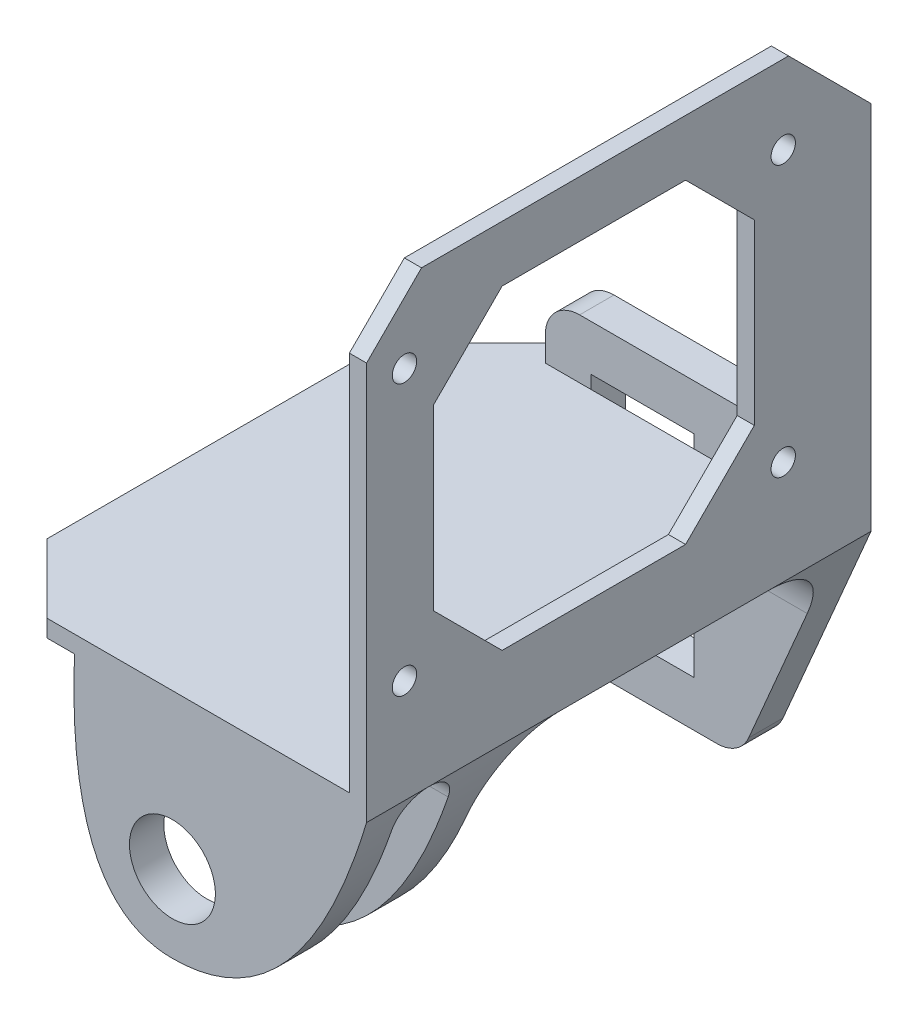
SolidWorks part; units mm, degrees
material "ABS PC"
ref_plane "Front Plane" through (0, 0, 0) normal (0, 0, 1) x (1, 0, 0)
ref_plane "Top Plane" through (0, 0, 0) normal (0, 1, 0) x (1, 0, 0)
ref_plane "Right Plane" through (0, 0, 0) normal (1, 0, 0) x (0, 0, -1)
sketch "Sketch1" plane through (0, 0, 0) normal (0, 1, 0) x (1, 0, 0)
  line L0 (0, 46.609) -> (71.755, 46.609) construction
  line L1 (0, 0) -> (71.755, 0)
  line L2 (0, 0) -> (0, 93.218)
  line L3 (0, 93.218) -> (71.755, 93.218)
  line L4 (71.755, 0) -> (71.755, 93.218)
  line L5 (35.8775, 93.218) -> (35.8775, 0) construction
  dimension "D1" = 71.755
  dimension "D2" = 93.218
extrude "Boss-Extrude1" add sketch "Sketch1" along normal blind 3.175
ref_plane "Plane2" through (0, 0, -46.609) normal (0, 0, -1) x (-1, 0, 0)
ref_plane "Plane1" through (35.8775, 0, 0) normal (1, 0, 0) x (0, 0, -1)
sketch "Sketch3" plane through (0, 3.175, 0) normal (0, 1, 0) x (1, 0, 0)
  line L0 (71.755, 0) -> (68.58, 0)
  line L1 (0, 0) -> (71.755, 0) construction
  line L2 (68.58, 0) -> (68.58, 93.218)
  line L3 (71.755, 93.218) -> (0, 93.218) construction
  line L4 (68.58, 93.218) -> (71.755, 93.218)
  line L5 (71.755, 93.218) -> (71.755, 0)
  dimension "D1" = 3.175
extrude "Boss-Extrude4" add sketch "Sketch3" along normal blind 80.518
sketch "Sketch8" plane through (0, 0, -46.609) normal (0, 0, 1) x (1, 0, 0)
  line L1 (0, 0) -> (71.755, 0) construction
  line L5 (35.8775, -46.0311) -> (35.8775, 46.0311) construction
  line L7 (35.8775, 0) -> (35.8775, -33.4) construction
  line L8 (45.3775, 0) -> (45.3775, -33.4)
  line L9 (45.3775, -33.4) -> (26.3775, -33.4)
  line L10 (26.3775, -33.4) -> (26.3775, 0)
  line L11 (45.3775, 0) -> (45.3775, 5.6)
  line L12 (45.3775, 5.6) -> (26.3775, 5.6)
  line L13 (26.3775, 5.6) -> (26.3775, 0)
  line L14 (17.9108, 14.0667) -> (17.9108, 0)
  line L15 (17.9108, -41.8667) -> (17.9108, 0)
  line L16 (53.8442, -41.8667) -> (17.9108, -41.8667)
  line L17 (53.8442, 0) -> (53.8442, -41.8667) construction
  line L18 (53.8442, 0) -> (53.8442, 14.0667) construction
  line L19 (53.8442, 14.0667) -> (17.9108, 14.0667)
  line L20 (53.8442, 14.0667) -> (71.755, 14.0667)
  line L21 (71.755, 83.693) -> (71.755, 0) construction
  line L22 (71.755, 14.0667) -> (71.755, 0)
  line L23 (71.755, 0) -> (53.8442, -41.8667)
  dimension "D3" = 8.4667
  dimension "D4" = 33.4
  dimension "D1" = 39
  dimension "D2" = 19
extrude "Boss-Extrude10" add sketch "Sketch8" along normal blind 6.35 from surface contours L22 L23 L16 L15 L14 L19 L20 L12 L13 L10 L9 L8 L11 starting at face at (46.7783, 28.956, -93.218)
sketch "Sketch16" plane through (0, 0, -93.218) normal (0, 0, -1) x (-1, 0, 0)
  line L8 (-45.3775, 5.6) -> (-45.3775, -33.4)
  line L9 (-45.3775, -33.4) -> (-26.3775, -33.4)
  line L10 (-26.3775, -33.4) -> (-26.3775, 5.6)
  line L11 (-26.3775, 5.6) -> (-45.3775, 5.6)
extrude "Cut-Extrude5" cut sketch "Sketch16" against normal blind 6.35
sketch "Sketch11" plane through (71.755, 0, 0) normal (1, 0, 0) x (0, 0, -1)
  line L7 (86.868, 0) -> (93.218, 0)
  line L8 (86.868, 0) -> (93.218, 0)
  line L9 (93.218, 83.693) -> (0, 83.693)
  line L11 (0, 83.693) -> (0, 0)
  line L16 (93.218, 0) -> (93.218, 83.693)
  line L17 (0, 0) -> (86.868, 0)
  line L18 (93.218, 83.693) -> (0, 83.693)
  line L20 (0, 83.693) -> (0, 0)
  line L25 (93.218, 0) -> (93.218, 83.693)
  line L28 (0, 0) -> (86.868, 0)
  arc A16 (77, 21.425) -> (77, 16.925) centre (77, 19.175) ccw construction
  arc A17 (77, 16.925) -> (77, 21.425) centre (77, 19.175) ccw construction
  arc A18 (7, 21.425) -> (7, 16.925) centre (7, 19.175) ccw construction
  arc A19 (7, 16.925) -> (7, 21.425) centre (7, 19.175) ccw construction
  arc A20 (7, 71.425) -> (7, 66.925) centre (7, 69.175) ccw construction
  arc A21 (7, 66.925) -> (7, 71.425) centre (7, 69.175) ccw construction
  arc A22 (77, 71.425) -> (77, 66.925) centre (77, 69.175) ccw construction
  arc A23 (77, 66.925) -> (77, 71.425) centre (77, 69.175) ccw construction
  arc A24 (77, 21.425) -> (77, 16.925) centre (77, 19.175) ccw
  arc A25 (77, 16.925) -> (77, 21.425) centre (77, 19.175) ccw
  arc A26 (7, 21.425) -> (7, 16.925) centre (7, 19.175) ccw
  arc A27 (7, 16.925) -> (7, 21.425) centre (7, 19.175) ccw
  arc A28 (7, 71.425) -> (7, 66.925) centre (7, 69.175) ccw
  arc A29 (7, 66.925) -> (7, 71.425) centre (7, 69.175) ccw
  arc A30 (77, 71.425) -> (77, 66.925) centre (77, 69.175) ccw
  arc A31 (77, 66.925) -> (77, 71.425) centre (77, 69.175) ccw
  dimension "D1" = 0
extrude "Cut-Extrude2" cut sketch "Sketch11" against normal up to next contours A28 A29 | A30 A31 | A24 A25 | A26 A27
sketch "Sketch9" plane through (71.755, 0, 0) normal (1, 0, 0) x (0, 0, -1)
  line L0 (86.868, 0) -> (86.868, 83.693) construction
  line L2 (12.3455, 15.0285) -> (71.6545, 15.0285)
  line L3 (12.3455, 15.0285) -> (12.3455, 73.3215)
  line L4 (12.3455, 73.3215) -> (71.6545, 73.3215)
  line L5 (71.6545, 15.0285) -> (71.6545, 73.3215)
  line L6 (12.3455, 15.0285) -> (71.6545, 73.3215) construction
  line L7 (12.3455, 73.3215) -> (71.6545, 15.0285) construction
  line L8 (0, 83.693) -> (93.218, 83.693) construction
  line L9 (7, 69.175) -> (77, 19.175) construction
  point P4 (42, 44.175)
  point P9 (42, 44.175)
  dimension "D1" = 59.309
  dimension "D5" = 58.293
extrude "Cut-Extrude1" cut sketch "Sketch9" against normal up to next contours L3 L2 L5 L4
chamfer "Chamfer1" distance 12.7 angle 45 4 edges at (70.1675, 15.0285, -12.3455) (70.1675, 15.0285, -71.6545) (70.1675, 73.3215, -71.6545) (70.1675, 73.3215, -12.3455)
fillet "Fillet3" radius 17.78 1 edges at (0, 1.5875, -93.218) profile chamfer
sketch "Sketch10" plane through (0, 0, 0) normal (0, 0, 1) x (1, 0, 0)
  line L0 (35.8775, -25.4) -> (35.8775, 0) construction
  line L7 (35.8775, -25.4) -> (35.8775, -39.6875) construction
  line L8 (71.755, 0) -> (17.78, 0)
  circle A0 centre (35.8775, -25.4) radius 7.9375
  circle A5 centre (35.8775, -25.4) radius 14.2875 construction
  spline S0 degree 2 poles (35.8775, -39.6875) (16.2478, -39.6875) (17.78, 0) knots 0 0 0 1 1 1
  spline S1 degree 2 poles (35.8775, -39.6875) (59.8112, -39.6875) (71.755, 0) knots 0 0 0 1 1 1
  point P2 (0, 0)
  dimension "D1" = 15.875
  dimension "D2" = 14.2875
  dimension "D3" = 25.4
extrude "Boss-Extrude11" add sketch "Sketch10" against normal blind 6.35 from surface starting at face at (46.7783, 28.956, 0)
pattern_linear "LPattern1" count 2 spacing 16.7132 along (0, 0, -1) of "Boss-Extrude11"
fillet "Fillet5" radius 6.35 3 edges at (53.8442, -41.8667, -90.043) (17.9108, 14.0667, -90.043) (17.9108, -41.8667, -90.043)
fillet "Fillet8" radius 5.08 2 edges at (44.7675, 0, -16.7132)
fillet "Fillet9" radius 12.7 3 edges at (44.7675, 0, -23.0632) (58.5663, 0, -86.868) (22.1442, 0, -86.868)
chamfer "Chamfer2" distance 15.24 angle 45 1 edges at (70.1675, 83.693, -93.218)
chamfer "Chamfer3" distance 10.16 angle 45 1 edges at (70.1675, 83.693, 0)
chamfer "Chamfer4" distance 12.7 angle 45 1 edges at (0, 1.5875, 0)
equation "\"D2@Sketch10\"=0.3125+0.25"
